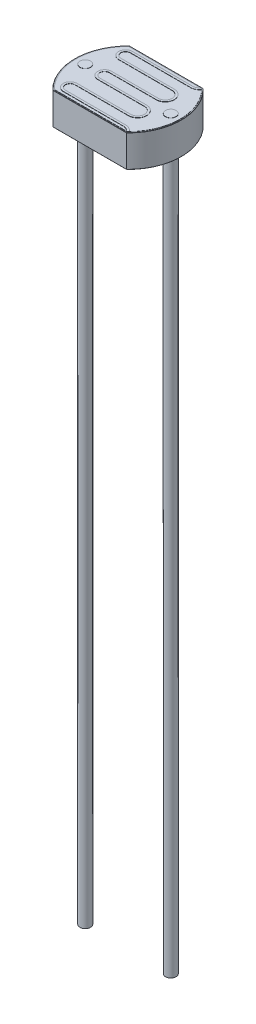
SolidWorks part; units mm, degrees
material "1060 Alloy"
ref_plane "Front Plane" through (0, 0, 0) normal (0, 0, 1) x (1, 0, 0)
ref_plane "Top Plane" through (0, 0, 0) normal (0, 1, 0) x (1, 0, 0)
ref_plane "Right Plane" through (0, 0, 0) normal (1, 0, 0) x (0, 0, -1)
sketch "Sketch1" plane through (0, 0, 0) normal (0, 1, 0) x (1, 0, 0)
  line L0 (-2.5, 0) -> (2.5, 0) construction
  line L1 (0, 0) -> (0, 1.8) construction
  line L2 (-1.7349, 1.8) -> (1.7349, 1.8)
  line L3 (-1.7349, -1.8) -> (1.7349, -1.8)
  line L4 (0, 2.5) -> (0, 45.783) construction
  arc A0 (1.7349, -1.8) -> (1.7349, 1.8) centre (0, 0) ccw
  arc A1 (-1.7349, 1.8) -> (-1.7349, -1.8) centre (0, 0) ccw
  dimension "D1" = 5
  dimension "D2" = 1.8
extrude "Boss-Extrude1" add sketch "Sketch1" along normal blind 1.5
sketch "Sketch2" plane through (0, 1.5, 0) normal (0, 1, 0) x (1, 0, 0)
  line L0 (-1.7146, -1.75) -> (1.7146, -1.75)
  line L1 (1.7146, 1.75) -> (-1.7146, 1.75)
  arc A0 (-1.7146, 1.75) -> (-1.7146, -1.75) centre (0, 0) ccw
  arc A1 (1.7146, -1.75) -> (1.7146, 1.75) centre (0, 0) ccw
extrude "Boss-Extrude2" add sketch "Sketch2" along normal blind 0.01
sketch "Sketch3" plane through (0, 1.51, 0) normal (0, 1, 0) x (1, 0, 0)
  line L0 (-1.4252, 0) -> (-1.1002, 0) construction
  line L1 (0, 1.75) -> (0, -1.75) construction
  line L2 (1.7146, 1.75) -> (-1.7146, 1.75) construction
  line L3 (-1.7146, -1.75) -> (1.7146, -1.75) construction
  line L4 (-1.1002, 1.75) -> (-1.1002, 1.625) construction
  line L5 (-1.7146, -1.75) -> (1.7146, -1.75) construction
  line L6 (1.1002, 1.625) -> (1.1002, -1.75) construction
  line L7 (-1.1002, 0.65) -> (0, 0.65) construction
  line L8 (-1.1002, -0.65) -> (0.7752, -0.65) construction
  line L9 (-1.1002, 0.325) -> (1.1002, 0.325)
  line L10 (-1.1002, -0.325) -> (1.1002, -0.325)
  line L11 (1.1002, -0.975) -> (-1.1002, -0.975)
  line L12 (1.1002, 0.975) -> (-1.1002, 0.975)
  line L13 (-1.1002, 0.975) -> (-1.4156, 0.975)
  line L14 (-1.1002, -0.975) -> (-1.4156, -0.975)
  line L15 (-1.4156, 1.625) -> (1.1002, 1.625)
  line L16 (-1.4156, -1.625) -> (1.1002, -1.625)
  line L17 (-1.1002, -1.625) -> (-1.1002, -1.75) construction
  line L18 (-0.7752, 0) -> (2.45, 0) construction
  line L19 (-1.1002, 0.975) -> (-1.1002, -0.975) construction
  line L20 (1.1002, 1.625) -> (1.4149, 1.625)
  line L21 (-1.4156, -1.525) -> (1.1002, -1.525)
  line L22 (-1.1002, -1.075) -> (-1.4156, -1.075)
  line L23 (1.1002, -1.075) -> (-1.1002, -1.075)
  line L24 (-1.1002, -0.225) -> (1.1002, -0.225)
  line L25 (-1.1002, 0.225) -> (1.1002, 0.225)
  line L26 (1.1002, 1.075) -> (-1.1002, 1.075)
  line L27 (-1.1002, 1.075) -> (-1.4156, 1.075)
  line L28 (-1.4156, 1.525) -> (1.1002, 1.525)
  line L29 (1.1002, 1.525) -> (1.4149, 1.525)
  line L30 (1.7146, 1.75) -> (1.671, 1.75)
  line L31 (1.1002, -1.625) -> (1.4149, -1.625)
  line L32 (1.1002, -1.525) -> (1.4149, -1.525)
  line L33 (1.7146, -1.75) -> (1.671, -1.75)
  arc A1 (1.7146, -1.75) -> (1.7146, 1.75) centre (0, 0) ccw construction
  arc A2 (-1.1002, 0.325) -> (-1.1002, -0.325) centre (-1.1002, 0) ccw
  arc A3 (1.1002, 0.325) -> (1.1002, 0.975) centre (1.1002, 0.65) ccw
  arc A4 (1.1002, -0.325) -> (1.1002, -0.975) centre (1.1002, -0.65) cw
  arc A5 (1.4149, 1.625) -> (1.671, 1.75) centre (1.4149, 1.95) ccw
  arc A6 (-1.4156, -1.625) -> (-1.4156, -0.975) centre (-1.4156, -1.3) cw
  arc A7 (-1.4156, 1.625) -> (-1.4156, 0.975) centre (-1.4156, 1.3) ccw
  arc A8 (-1.4156, -1.525) -> (-1.4156, -1.075) centre (-1.4156, -1.3) cw
  arc A9 (1.1002, -0.225) -> (1.1002, -1.075) centre (1.1002, -0.65) cw
  arc A10 (-1.1002, 0.225) -> (-1.1002, -0.225) centre (-1.1002, 0) ccw
  arc A11 (1.1002, 0.225) -> (1.1002, 1.075) centre (1.1002, 0.65) ccw
  arc A12 (-1.4156, 1.525) -> (-1.4156, 1.075) centre (-1.4156, 1.3) ccw
  arc A13 (1.4149, -1.525) -> (1.761, -1.7034) centre (1.4149, -1.95) cw
  arc A14 (1.761, -1.7034) -> (1.7146, -1.75) centre (0, 0) cw
  arc A15 (1.4149, -1.625) -> (1.671, -1.75) centre (1.4149, -1.95) cw
  arc A17 (1.761, 1.7034) -> (1.7146, 1.75) centre (0, 0) ccw
  arc A18 (1.4149, 1.525) -> (1.761, 1.7034) centre (1.4149, 1.95) ccw
  dimension "D1" = 0.65
  dimension "D2" = 0.65
  dimension "D3" = 0.3146
  dimension "D4" = 0.65
  dimension "D5" = 0.1
extrude "Boss-Extrude3" add sketch "Sketch3" along normal blind 0.01
sketch "Sketch4" plane through (0, 1.51, 0) normal (0, 1, 0) x (1, 0, 0)
  line L0 (-2.5, 0) -> (0, 0) construction
  line L1 (0, 0) -> (0, 0.6491) construction
  arc A0 (-1.7349, 1.8) -> (-1.7349, -1.8) centre (0, 0) ccw construction
  circle A1 centre (-2.0097, 0) radius 0.25
  circle A2 centre (2.0097, 0) radius 0.25
  dimension "D1" = 0.5
extrude "Boss-Extrude4" add sketch "Sketch4" along normal blind 0.01 and the other way blind 35
fillet "Fillet1" radius 0.01 11 edges at (1.7349, 0.75, -1.8) (0, 1.5, -1.8) (0, 0, -1.8) (2.5, 0, 0) (2.5, 1.5, 0) (1.7349, 0.75, 1.8) (0, 0, 1.8) (0, 1.5, 1.8) (-1.7349, 0.75, 1.8) (-2.5, 0, 0) (-2.5, 1.5, 0)
